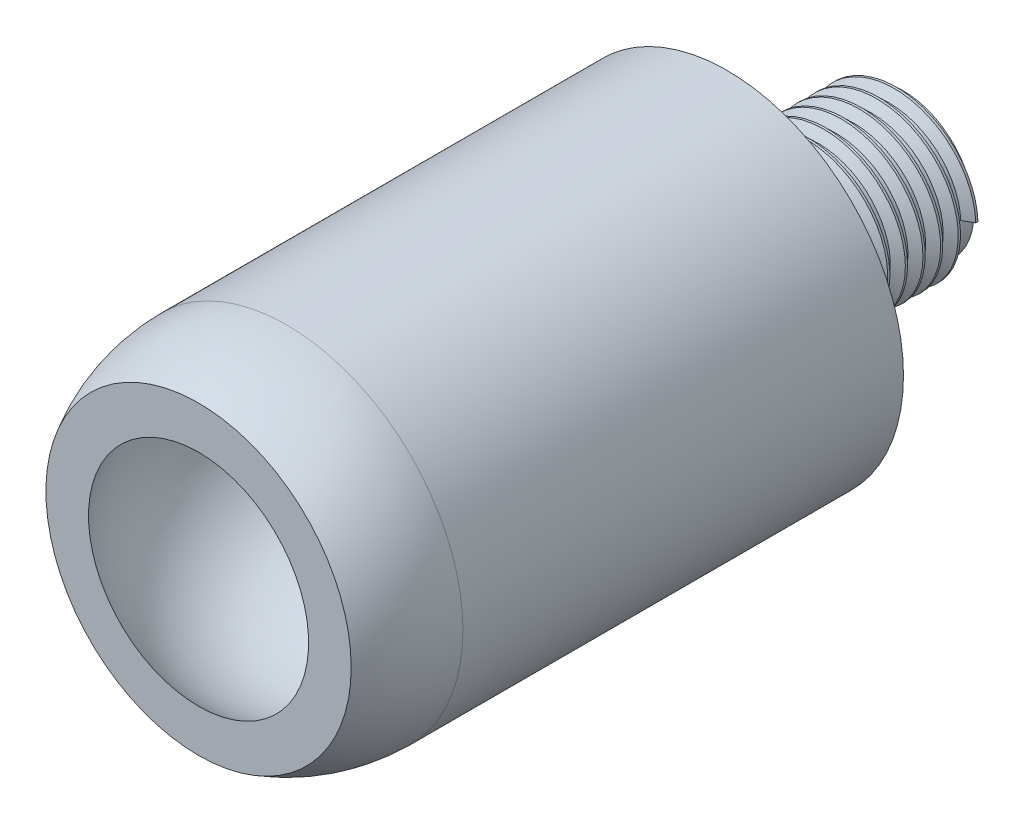
SolidWorks part; units mm, degrees
ref_plane "Front Plane" through (0, 0, 0) normal (0, 0, 1) x (1, 0, 0)
ref_plane "Top Plane" through (0, 0, 0) normal (0, 1, 0) x (1, 0, 0)
ref_plane "Right Plane" through (0, 0, 0) normal (1, 0, 0) x (0, 0, -1)
sketch "Sketch1" plane through (0, 0, 0) normal (0, 0, 1) x (1, 0, 0)
  circle A0 centre (0, 0) radius 10
  dimension "D1" = 20
extrude "Boss-Extrude1" add sketch "Sketch1" along normal blind 25
sketch "Sketch2" plane through (0, 0, 0) normal (0, 0, -1) x (-1, 0, 0)
  circle A0 centre (0, 0) radius 4
  dimension "D1" = 8
extrude "Boss-Extrude2" add sketch "Sketch2" along normal blind 10
thread "Thread1" pitch 1 method extrude profile "Thread Profile1" start angle 0, offset 0, length 0, pitch 1, diameter 8
ref_plane "Plane1" through (4, 0, -10) normal (0, -1, 0) x (1, 0, 0)
sketch "Thread Profile1" plane through (4, 0, -10) normal (0, -1, 0) x (1, 0, 0)
  line L0 (0, 0) -> (0, 1) construction
  line L1 (0, 0) -> (0.5413, 0.3125)
  line L2 (0.5413, 0.3125) -> (0.5413, 0.4375)
  line L3 (0.5413, 0.4375) -> (0, 0.75)
  line L4 (0.5413, 0.375) -> (0, 0.375) construction
  line L11 (0, 0) -> (0, 0.75)
  point P2 (0, 0)
  dimension "Pitch" = 1
  dimension "Profile_Angle" = 60
  dimension "Profile_Land" = 0.125
  dimension "Profile_Height" = 0.5413
sketch "Sketch7" plane through (0, 0, 0) normal (1, 0, 0) x (0, 0, -1)
  line L0 (-25, 10) -> (-25, -10) construction
  line L1 (-25, 10) -> (-25, 0)
  line L2 (-25, 0) -> (-15, 0)
  arc A0 (-25, 10) -> (-15, 0) centre (-25, 0) cw
revolve "Cut-Revolve1" cut sketch "Sketch7" angle 360 about L2
sketch "Sketch8" plane through (0, 0, 0) normal (1, 0, 0) x (0, 0, -1)
  line L0 (-25, 10) -> (-25, -10) construction
  line L1 (-15, 0) -> (-17, 0)
  line L2 (-30, 8.6603) -> (-30, 6.245)
  line L3 (-25, 0) -> (-30, 8.6603)
  line L4 (-25, 0) -> (-17, 0)
  arc A0 (-30, 8.6603) -> (-15, 0) centre (-25, 0) cw
  arc A1 (-30, 6.245) -> (-17, 0) centre (-25, 0) cw
  dimension "D1" = 10
  dimension "D2" = 8
  dimension "D3" = 60
revolve "Revolve2" add sketch "Sketch8" angle 360 about L4 region at (0, 0.1803, 16) region at (0, 7.2885, 29.6692)
